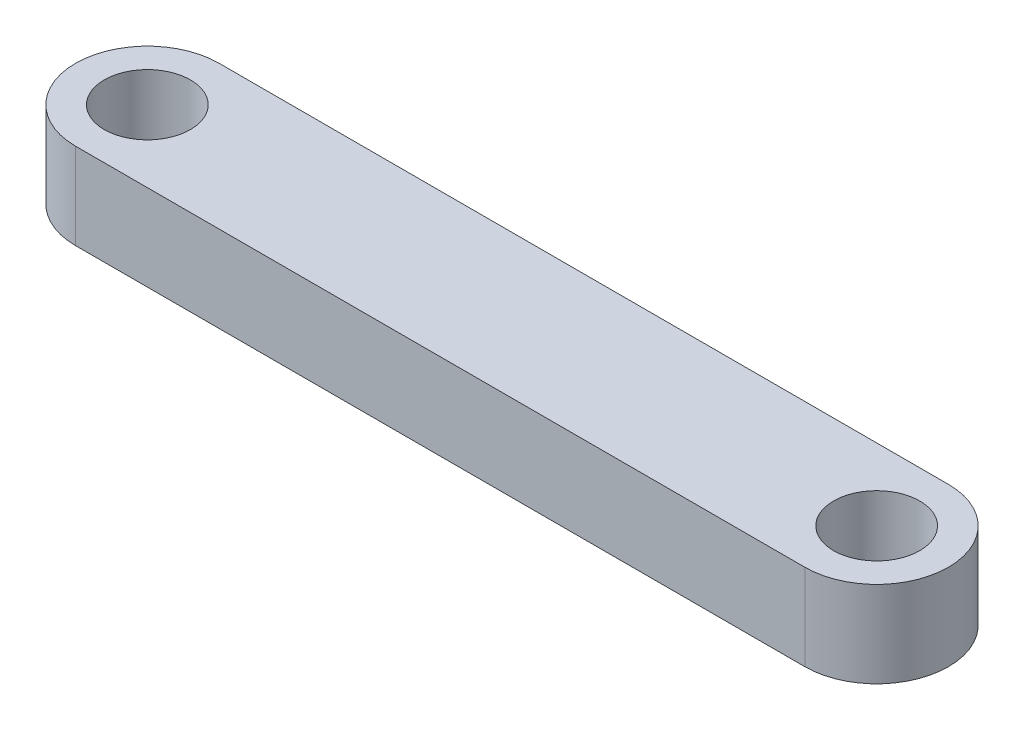
SolidWorks part; units mm, degrees
ref_plane "Front Plane" through (0, 0, 0) normal (0, 0, 1) x (1, 0, 0)
ref_plane "Top Plane" through (0, 0, 0) normal (0, 1, 0) x (1, 0, 0)
ref_plane "Right Plane" through (0, 0, 0) normal (1, 0, 0) x (0, 0, -1)
sketch "Sketch1" plane through (0, 0, 0) normal (0, 1, 0) x (1, 0, 0)
  line L0 (-12.7, 0) -> (12.7, 0) construction
  line L1 (-15.2, 2.5) -> (-12.7, 2.5) construction
  line L2 (-12.7, 2.5) -> (12.7, 2.5)
  line L3 (-15.2, 2.5) -> (-15.2, -2.5) construction
  line L4 (-12.7, -2.5) -> (12.7, -2.5)
  line L5 (15.2, 2.5) -> (15.2, -2.5) construction
  line L6 (-13.7616, 2.2634) -> (13.7616, -2.2634) construction
  line L7 (-13.7616, -2.2634) -> (13.7616, 2.2634) construction
  line L8 (-15.2, 2.5) -> (-13.7616, 2.2634) construction
  line L9 (-15.2, -2.5) -> (-13.7616, -2.2634) construction
  line L10 (-15.2, -2.5) -> (-12.7, -2.5) construction
  line L11 (12.7, 2.5) -> (15.2, 2.5) construction
  line L12 (13.7616, 2.2634) -> (15.2, 2.5) construction
  line L13 (12.7, -2.5) -> (15.2, -2.5) construction
  line L14 (13.7616, -2.2634) -> (15.2, -2.5) construction
  circle A0 centre (-12.7, 0) radius 1.5
  circle A1 centre (12.7, 0) radius 1.5
  arc A2 (-12.7, 2.5) -> (-12.7, -2.5) centre (-12.7, 0) ccw
  arc A3 (12.7, -2.5) -> (12.7, 2.5) centre (12.7, 0) ccw
  point P4 (0, 0)
  point P10 (0, 0)
  point P18 (0, 0)
  point P21 (0, 0)
  dimension "D1" = 3
  dimension "D2" = 25.4
  dimension "D4" = 5
  dimension "D3" = 25.4
extrude "Boss-Extrude2" add sketch "Sketch1" along normal mid plane 3
